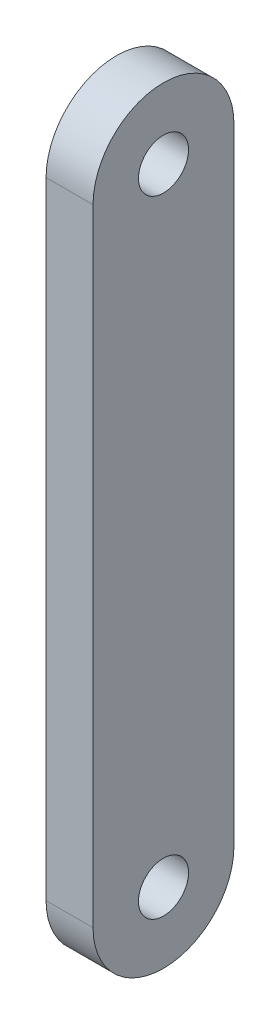
SolidWorks part; units mm, degrees
ref_plane "Front Plane" through (0, 0, 0) normal (0, 0, 1) x (1, 0, 0)
ref_plane "Top Plane" through (0, 0, 0) normal (0, 1, 0) x (1, 0, 0)
ref_plane "Right Plane" through (0, 0, 0) normal (1, 0, 0) x (0, 0, -1)
sketch "Sketch1" plane through (0, 0, 0) normal (1, 0, 0) x (0, 0, -1)
  line L0 (-4.5, 0) -> (-4.5, 40)
  line L1 (4.5, 0) -> (4.5, 40)
  arc A0 (4.5, 0) -> (-4.5, 0) centre (0, 0) cw
  arc A1 (4.5, 40) -> (-4.5, 40) centre (0, 40) ccw
  circle A2 centre (0, 40) radius 1.6
  circle A3 centre (0, 0) radius 1.6
  dimension "D1" = 4.5
  dimension "D2" = 3.2
  dimension "D3" = 40
extrude "Boss-Extrude1" add sketch "Sketch1" along normal blind 3
